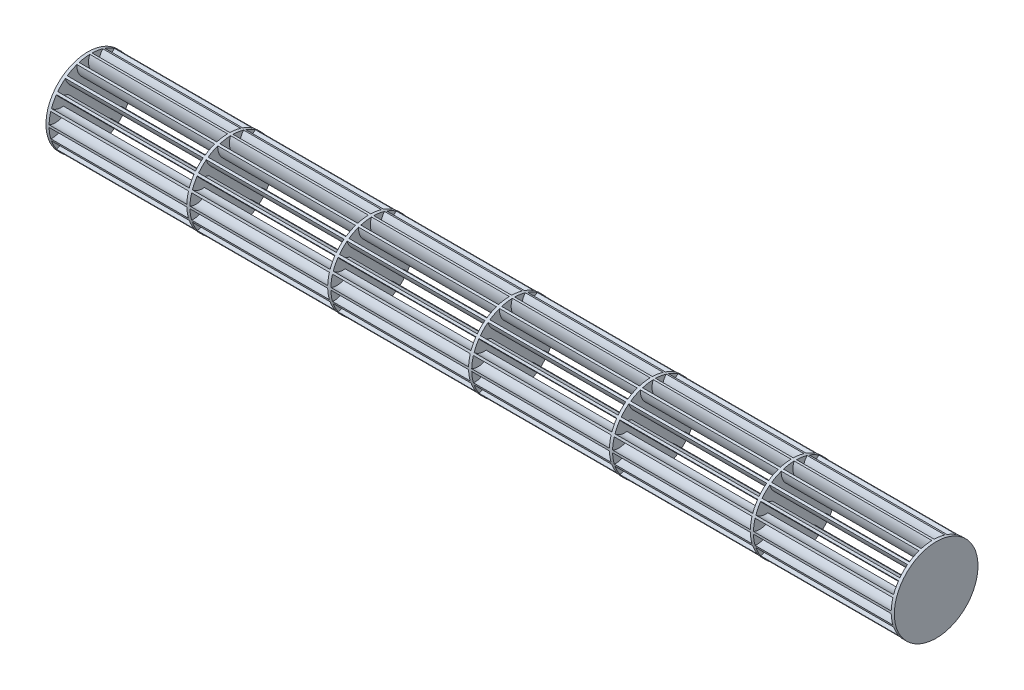
SolidWorks part; units mm, degrees
ref_plane "Front Plane" through (0, 0, 0) normal (0, 0, 1) x (1, 0, 0)
ref_plane "Top Plane" through (0, 0, 0) normal (0, 1, 0) x (1, 0, 0)
ref_plane "Right Plane" through (0, 0, 0) normal (1, 0, 0) x (0, 0, -1)
ref_plane "Plane2" through (202, 0, 0) normal (1, 0, 0) x (0, 0, -1)
sketch "Sketch2" plane through (202, 0, 0) normal (1, 0, 0) x (0, 0, -1)
  circle A0 centre (0, 0) radius 20
  dimension "D1" = 40
extrude "Boss-Extrude2" add sketch "Sketch2" against normal blind 1.5
sketch "Sketch1" plane through (0, 0, 0) normal (1, 0, 0) x (0, 0, -1)
  line L0 (-0.5459, 19.9925) -> (0.5459, 19.9925) construction
  arc A0 (0.5459, 19.9925) -> (-0.5459, 19.9925) centre (0, 0) ccw
  arc A1 (0.5459, 19.9925) -> (0.5459, 13.9894) centre (6.8697, 16.991) ccw
  arc A2 (-0.5459, 19.9925) -> (-0.5459, 13.9894) centre (6.8697, 16.991) ccw
  arc A3 (0.5459, 13.9894) -> (-0.5459, 13.9894) centre (0, 0) ccw
  arc A4 (-0.5459, 19.9925) -> (0.5459, 19.9925) centre (0, 0) ccw construction
  point P11 (0, 14)
  dimension "D1" = 40
  dimension "D4" = 8
  dimension "D2" = 1
  dimension "D3" = 6
extrude "Boss-Extrude1" add sketch "Sketch1" along normal mid plane 404
pattern_circular "CirPattern1" count 20 over 360 about axis through (202, 0, 0) along (1, 0, 0) of "Boss-Extrude1"
pattern_linear "LPattern1" count 7 spacing 67.3333 along (-1, 0, 0) of "Boss-Extrude2"
equation "\"A\"= 420mm"
equation "\"num_segments\"= 6"
equation "\"end_clearance\"= 8mm"
equation "\"impeller_diameter\"= 40mm"
equation "\"D1@Sketch1\"=\"impeller_diameter\""
equation "\"D1@Boss-Extrude1\"=\"A\"-(2*\"end_clearance\")"
equation "\"D1@Plane2\"=(\"A\"/2)-\"end_clearance\""
equation "\"D1@Sketch2\"=\"impeller_diameter\""
equation "\"D1@LPattern1\"=\"num_segments\"+1"
